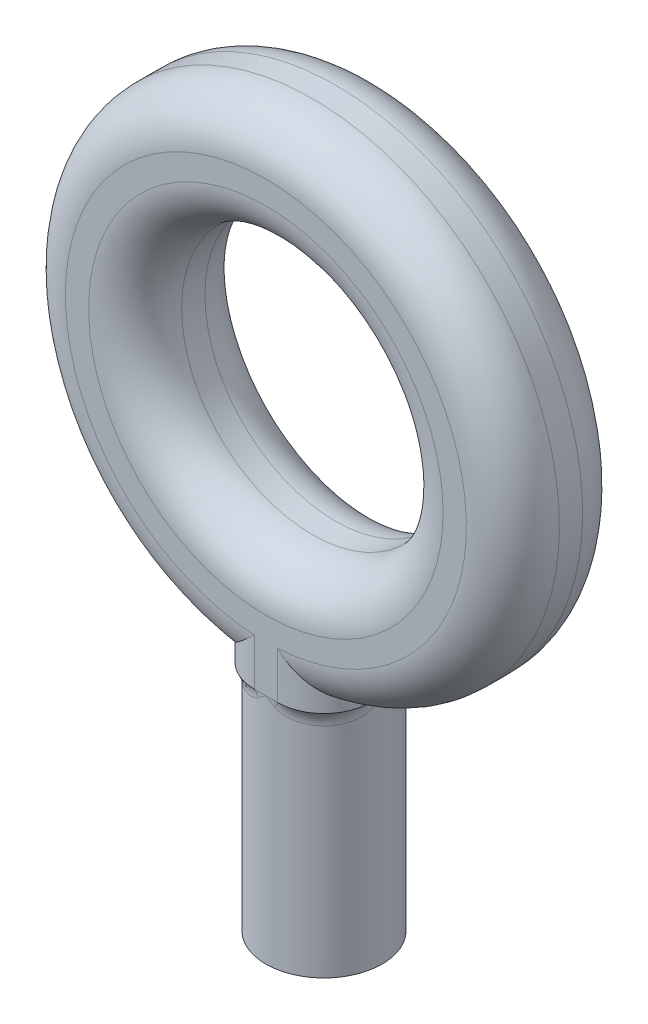
SolidWorks part; units mm, degrees
ref_plane "Front Plane" through (0, 0, 0) normal (0, 0, 1) x (1, 0, 0)
ref_plane "Top Plane" through (0, 0, 0) normal (0, 1, 0) x (1, 0, 0)
ref_plane "Right Plane" through (0, 0, 0) normal (1, 0, 0) x (0, 0, -1)
sketch "Sketch1" plane through (0, 0, 0) normal (0, 1, 0) x (1, 0, 0)
  circle A0 centre (0, 0) radius 2.5
  dimension "D1" = 5
extrude "Boss-Extrude1" add sketch "Sketch1" along normal blind 10
sketch "Sketch2" plane through (0, 0, 0) normal (0, 0, 1) x (1, 0, 0)
  line L0 (2.5, 10) -> (-2.5, 10) construction
  line L1 (-2.5, 10) -> (-2.5, 10.2983)
  line L2 (-2.5, 10) -> (2.5, 10)
  line L3 (2.5, 10) -> (2.5, 10.2983)
  circle A0 centre (0, 20.625) radius 5.625
  arc A1 (2.5, 10.2983) -> (-2.5, 10.2983) centre (0, 20.625) ccw
  dimension "D1" = 11.25
  dimension "D2" = 10.625
extrude "Boss-Extrude2" add sketch "Sketch2" along normal blind 2.5 and the other way blind 2.5
fillet "Fillet1" radius 2 4 edges at (5.625, 20.625, -2.5) (5.625, 20.625, 2.5) (0, 31.25, -2.5) (0, 31.25, 2.5)
fillet "Fillet2" radius 2 4 edges at (2.5, 11.1851, -2.5) (-2.5, 11.1851, -2.5) (-2.5, 11.1851, 2.5) (2.5, 11.1851, 2.5)
fillet "Fillet3" radius 1 4 edges at (1.7678, 10, -1.7678) (1.7678, 10, 1.7678) (-1.7678, 10, 1.7678) (-1.7678, 10, -1.7678)
